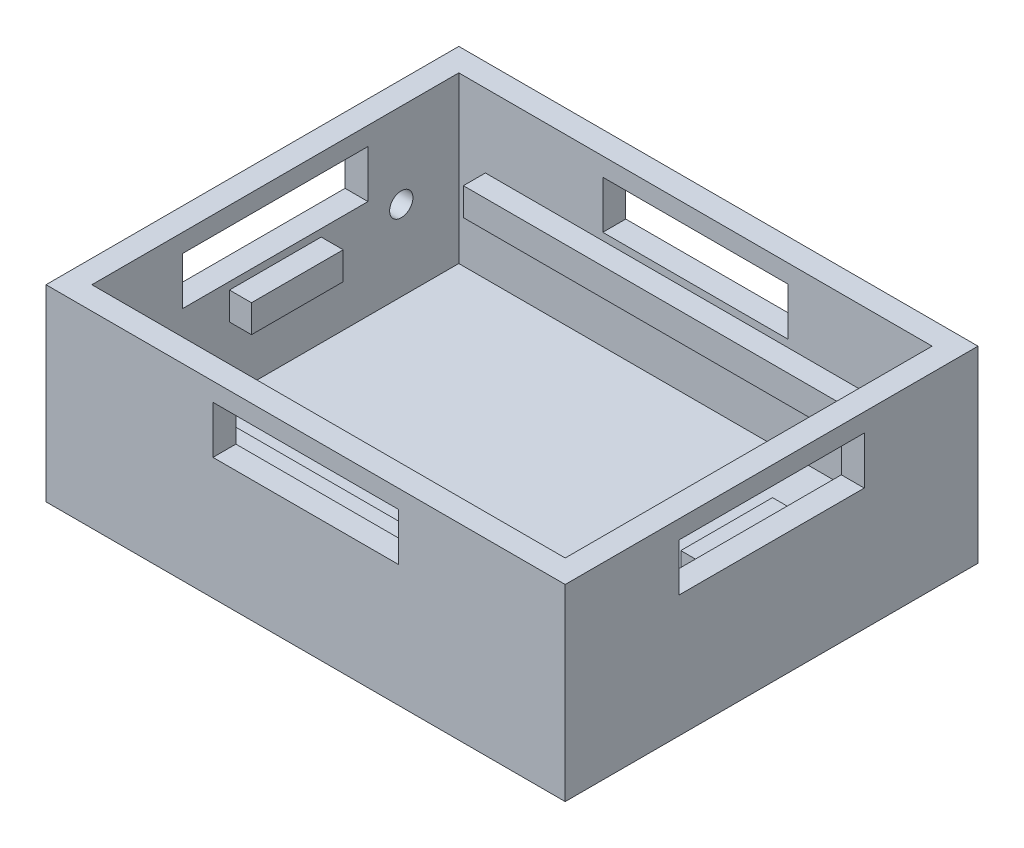
SolidWorks part; units mm, degrees
ref_plane "Front Plane" through (0, 0, 0) normal (0, 0, 1) x (1, 0, 0)
ref_plane "Top Plane" through (0, 0, 0) normal (0, 1, 0) x (1, 0, 0)
ref_plane "Right Plane" through (0, 0, 0) normal (1, 0, 0) x (0, 0, -1)
sketch "Sketch1" plane through (0, 0, 0) normal (0, 1, 0) x (1, 0, 0)
  line L0 (-2.5, 2.5) -> (-2.5, 202.5)
  line L5 (-15, -10) -> (268, -10)
  line L6 (-15, -10) -> (-15, 215)
  line L7 (-15, 215) -> (268, 215)
  line L8 (268, -10) -> (268, 215)
  line L9 (-2.5, 202.5) -> (255.5, 202.5)
  line L10 (255.5, 2.5) -> (255.5, 202.5)
  line L11 (-2.5, 2.5) -> (255.5, 2.5)
  dimension "D1" = 283
  dimension "D2" = 225
  dimension "D3" = 12.5
extrude "Walls" add sketch "Sketch1" along normal blind 90
sketch "Sketch3" plane through (0, 0, 0) normal (0, -1, 0) x (1, 0, 0)
  line L0 (268, -215) -> (-15, -215) construction
  line L1 (268, 10) -> (268, -215) construction
  line L2 (-15, 10) -> (268, 10) construction
  line L3 (-15, -215) -> (-15, 10) construction
  line L4 (268, -215) -> (-15, -215)
  line L5 (268, 10) -> (268, -215)
  line L6 (-15, 10) -> (268, 10)
  line L7 (-15, -215) -> (-15, 10)
extrude "Base" add sketch "Sketch3" along normal blind 12.5
ref_plane "Long_Support_Midplane" through (126.5, 0, 0) normal (1, 0, 0) x (0, 0, -1)
sketch "Sketch4" plane through (126.5, 0, 0) normal (1, 0, 0) x (0, 0, -1)
  line L0 (2.5, 0) -> (2.5, 90)
  line L1 (2.5, 50) -> (14.5, 50)
  line L2 (2.5, 50) -> (2.5, 34.9)
  line L3 (2.5, 34.9) -> (14.5, 34.9)
  line L4 (14.5, 50) -> (14.5, 34.9)
  line L5 (2.5, 0) -> (2.5, 90) construction
  line L6 (202.5, 50) -> (190.5, 50)
  line L7 (202.5, 50) -> (202.5, 34.9)
  line L8 (202.5, 34.9) -> (190.5, 34.9)
  line L9 (190.5, 50) -> (190.5, 34.9)
  line L14 (2.5, 0) -> (202.5, 0)
  line L15 (202.5, 0) -> (202.5, 90)
  line L16 (202.5, 90) -> (2.5, 90)
  line L17 (2.5, 90) -> (2.5, 0)
  line L18 (2.5, 0) -> (202.5, 0) construction
  line L19 (202.5, 0) -> (202.5, 90) construction
  line L20 (202.5, 90) -> (2.5, 90) construction
  line L21 (2.5, 90) -> (2.5, 0) construction
  dimension "D1" = 15.1
  dimension "D2" = 12
  dimension "D4" = 50
extrude "Long_Support" add sketch "Sketch4" along normal mid plane 229
ref_plane "Short_Support_Midplane" through (0, 0, -102.5) normal (0, 0, -1) x (-1, 0, 0)
sketch "Sketch5" plane through (0, 0, -102.5) normal (0, 0, -1) x (-1, 0, 0)
  line L1 (-255.5, 50) -> (-243.5, 50)
  line L2 (-255.5, 50) -> (-255.5, 34.9)
  line L3 (-255.5, 34.9) -> (-243.5, 34.9)
  line L4 (-243.5, 50) -> (-243.5, 34.9)
  line L5 (2.5, 50) -> (-9.5, 50)
  line L6 (2.5, 50) -> (2.5, 34.9)
  line L7 (2.5, 34.9) -> (-9.5, 34.9)
  line L8 (-9.5, 50) -> (-9.5, 34.9)
  line L12 (-255.5, 0) -> (2.5, 0)
  line L13 (2.5, 0) -> (2.5, 90)
  line L14 (2.5, 90) -> (-255.5, 90)
  line L15 (2.5, 0) -> (2.5, 90) construction
  line L16 (-255.5, 0) -> (2.5, 0) construction
  line L20 (-255.5, 90) -> (-255.5, 0)
  line L21 (-255.5, 90) -> (-255.5, 0) construction
  line L22 (2.5, 90) -> (-255.5, 90) construction
  dimension "D4" = 50
  dimension "D2" = 15.1
extrude "Short_Support" add sketch "Sketch5" along normal mid plane 50
sketch "Sketch6" plane through (-2.5, 0, 0) normal (1, 0, 0) x (0, 0, -1)
  line L4 (2.5, 0) -> (202.5, 0)
  line L5 (202.5, 0) -> (202.5, 90)
  line L6 (202.5, 90) -> (2.5, 90)
  line L7 (2.5, 90) -> (2.5, 0)
  line L8 (2.5, 0) -> (202.5, 0) construction
  line L9 (202.5, 0) -> (202.5, 90) construction
  line L10 (202.5, 90) -> (2.5, 90) construction
  line L11 (2.5, 90) -> (2.5, 0) construction
  circle A0 centre (171.15, 43.65) radius 6.35
  dimension "D2" = 12.7
  dimension "D3" = 31.35
  dimension "D4" = 43.65
extrude "Cut-Extrude4" cut sketch "Sketch6" against normal up to next
sketch "Sketch7" plane through (-2.5, 0, 0) normal (1, 0, 0) x (0, 0, -1)
  line L0 (127.5, 50) -> (77.5, 50) construction
  line L1 (52, 54) -> (153, 54)
  line L2 (52, 54) -> (52, 80)
  line L3 (52, 80) -> (153, 80)
  line L4 (153, 54) -> (153, 80)
  line L5 (202.5, 90) -> (2.5, 90) construction
  line L7 (102.5, 80) -> (102.5, 54) construction
  line L8 (102.5, -27.5) -> (102.5, 27.5) construction
  dimension "D1" = 4
  dimension "D2" = 10
  dimension "D3" = 26
  dimension "D4" = 101
extrude "Cut-Extrude5" cut sketch "Sketch7" against normal up to surface (12.5 mm away) up to face at (-15, 43.65, -177.5)
pattern_linear "LPattern1" count 2 spacing 270.5 along (1, 0, 0) of "Cut-Extrude5"
sketch "Sketch8" plane through (0, 0, -2.5) normal (0, 0, 1) x (1, 0, 0)
  line L1 (76, 54) -> (177, 54)
  line L2 (76, 54) -> (76, 80)
  line L3 (76, 80) -> (177, 80)
  line L4 (177, 54) -> (177, 80)
  line L6 (241, 50) -> (12, 50) construction
  line L7 (126.5, 80) -> (126.5, 54) construction
  line L9 (-2.5, 90) -> (255.5, 90) construction
  line L10 (126.5, -28.05) -> (126.5, 28.05) construction
  dimension "D3" = 26
  dimension "D4" = 101
  dimension "D1" = 4
  dimension "D2" = 10
extrude "Cut-Extrude6" cut sketch "Sketch8" along normal up to surface (12.5 mm away) contours L4 L3 L2 L1 up to face at (126.5, 38.75, 10)
pattern_linear "LPattern2" count 2 spacing 212.5 along (0, 0, -1) of "Cut-Extrude6"
equation "\"Length\" = 283"
equation "\"Width\" = 225"
equation "\"WallThickness\" = 12.5"
equation "\"UpperWaterJacketThickness\" = 28"
equation "\"SpacerHeight\" = 80.2"
equation "\"PlateLength\"=252"
equation "\"PlateWidth\"=190"
equation "\"PlateHoleDiameter\"=5.9"
equation "\"PlateHoleBottom\"= 2"
equation "\"PlateHoleSide\"= 1.55"
equation "\"PlateHoleSpacing\"= 3.1"
equation "\"PlateThickness\"=1.55"
equation "\"D1@Sketch1\"=\"Length\""
equation "\"D2@Sketch1\"=\"Width\""
equation "\"D3@Sketch1\"=\"WallThickness\""
equation "\"ReservoirBottom\"=12.5"
equation "\"D1@Base\"=\"ReservoirBottom\""
equation "\"ReservoirSupportWidth\"=12"
equation "\"D2@Sketch4\"=\"ReservoirSupportWidth\""
equation "\"ReservoirSupportHeight\"=15.1"
equation "\"D1@Sketch4\"=\"ReservoirSupportHeight\""
equation "\"D1@Sketch5\"=\"ReservoirSupportWidth\""
equation "\"D2@Sketch5\"=\"ReservoirSupportHeight\""
equation "\"ReservoirSupportPlacementHeight\"=50"
equation "\"D4@Sketch5\"=\"ReservoirSupportPlacementHeight\""
equation "\"D4@Sketch4\"=\"ReservoirSupportPlacementHeight\""
equation "\"ReservoirHoleDiameter\"=12.7"
equation "\"D2@Sketch6\"=\"ReservoirHoleDiameter\""
equation "\"ReservoirHoleRight\"= 25"
equation "\"D3@Sketch6\"=\"ReservoirHoleRight\"+\"ReservoirHoleDiameter\"/2"
equation "\"ReservoirHoleTop\" = \"ReservoirSupportPlacementHeight\""
equation "\"D4@Sketch6\"=\"ReservoirHoleTop\"-\"ReservoirHoleDiameter\"/2"
equation "\"ReservoirHeight\"=90"
equation "\"D1@Walls\"=\"ReservoirHeight\""
equation "\"ReservoirPortBottom\"=4"
equation "\"D1@Sketch7\"=\"ReservoirPortBottom\""
equation "\"ReservoirPortTop\" = 10"
equation "\"D2@Sketch7\"=\"ReservoirPortTop\""
equation "\"ReservoirPortWidth\"=101"
equation "\"D4@Sketch7\"=\"ReservoirPortWidth\""
equation "\"D4@Sketch8\"=\"ReservoirPortWidth\""
equation "\"D1@Sketch8\"=\"ReservoirPortBottom\""
equation "\"D2@Sketch8\"=\"ReservoirPortTop\""
